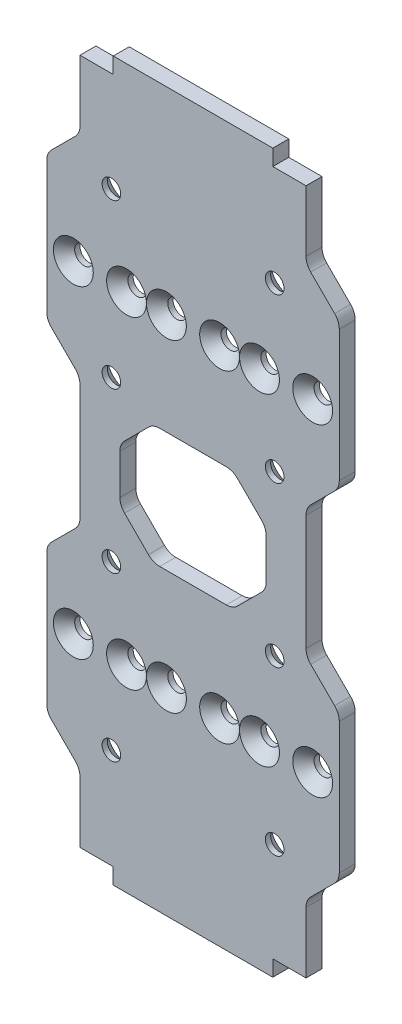
SolidWorks part; units mm, degrees
material "ABS"
ref_plane "Спереди" through (0, 0, 0) normal (0, 0, 1) x (1, 0, 0)
ref_plane "Сверху" through (0, 0, 0) normal (0, 1, 0) x (1, 0, 0)
ref_plane "Справа" through (0, 0, 0) normal (1, 0, 0) x (0, 0, -1)
sketch "Эскиз1" plane through (0, 0, 0) normal (0, 0, 1) x (1, 0, 0)
  line L0 (-27.5, 0) -> (27.5, 0) construction
  line L1 (-27.5, -64.5) -> (27.5, -64.5)
  line L2 (-27.5, -64.5) -> (-27.5, 64.5)
  line L3 (-27.5, 64.5) -> (27.5, 64.5)
  line L4 (27.5, -64.5) -> (27.5, 64.5)
  line L5 (-27.5, -64.5) -> (27.5, 64.5) construction
  line L6 (-27.5, 64.5) -> (27.5, -64.5) construction
  line L7 (-15, 61.5) -> (15, 61.5)
  line L8 (-15, 61.5) -> (-15, 67.5)
  line L9 (-15, 67.5) -> (15, 67.5)
  line L10 (15, 61.5) -> (15, 67.5)
  line L11 (-15, 61.5) -> (15, 67.5) construction
  line L12 (-15, 67.5) -> (15, 61.5) construction
  line L13 (-15, -67.5) -> (15, -61.5) construction
  line L14 (-15, -61.5) -> (15, -67.5) construction
  line L15 (15, -61.5) -> (15, -67.5)
  line L16 (-15, -67.5) -> (15, -67.5)
  line L17 (-15, -61.5) -> (-15, -67.5)
  line L18 (-15, -61.5) -> (15, -61.5)
  point P0 (0, 0)
  point P6 (0, 64.5)
  point P17 (0, -64.5)
  dimension "D1" = 3
  dimension "D2" = 30
  dimension "D3" = 12.5
  dimension "D4" = 129
extrude "Бобышка-Вытянуть1" add sketch "Эскиз1" along normal blind 3 contours L10 L7 L8 L3 L2 L1 L4 | L7 L10 L3 L8 | L3 L10 L9 L8 | L18 L17 L1 L15 | L1 L17 L16 L15 region at (0, 0, 0) region at (0, -63, 0) region at (0, -66, 0) region at (0, 66, 0) region at (0, 63, 0)
sketch "Эскиз2" plane through (0, 0, 3) normal (0, 0, 1) x (1, 0, 0)
  line L0 (0, 67.5) -> (0, -67.5) construction
  line L1 (-15, 67.5) -> (15, 67.5) construction
  line L3 (-27.5, 0) -> (27.5, 0) construction
  line L4 (-27.5, -64.5) -> (-27.5, 64.5) construction
  line L5 (27.5, -64.5) -> (27.5, 64.5) construction
  line L6 (-15.35, -15) -> (15.35, -45.7) construction
  line L7 (-15.35, 45.7) -> (15.35, 45.7) construction
  line L8 (-15.35, 45.7) -> (-15.35, 15) construction
  line L9 (-15.35, 15) -> (15.35, 15) construction
  line L10 (15.35, 45.7) -> (15.35, 15) construction
  line L11 (-15.35, 45.7) -> (15.35, 15) construction
  line L12 (-15.35, 15) -> (15.35, 45.7) construction
  line L13 (-15.35, -45.7) -> (15.35, -15) construction
  line L14 (15.35, -45.7) -> (15.35, -15) construction
  line L15 (-15.35, -15) -> (15.35, -15) construction
  line L16 (-15.35, -45.7) -> (-15.35, -15) construction
  line L17 (-15.35, -45.7) -> (15.35, -45.7) construction
  line L18 (-15, -67.5) -> (15, -67.5) construction
  circle A0 centre (-15.35, 45.7) radius 1.75
  circle A1 centre (15.35, 45.7) radius 1.75
  circle A2 centre (15.35, 15) radius 1.75
  circle A3 centre (-15.35, 15) radius 1.75
  circle A4 centre (-15.35, -15) radius 1.75
  circle A5 centre (15.35, -15) radius 1.75
  circle A6 centre (15.35, -45.7) radius 1.75
  circle A7 centre (-15.35, -45.7) radius 1.75
  point P4 (0, -65.5)
  point P12 (0, 30.35)
  point P29 (0, -30.35)
  dimension "D3" = 3.5
  dimension "D1" = 30.7
  dimension "D2" = 30.7
  dimension "D4" = 15
extrude "Вырез-Вытянуть1" cut sketch "Эскиз2" against normal blind 10
sketch "Эскиз3" plane through (0, 0, 0) normal (0, 0, -1) x (-1, 0, 0)
  line L0 (-15.35, 15) -> (15.35, 45.7) construction
  line L1 (-27.5, 30.35) -> (27.5, 30.35) construction
  line L2 (-27.5, -64.5) -> (-27.5, 64.5) construction
  line L3 (27.5, -64.5) -> (27.5, 64.5) construction
  line L4 (-27.5, 0) -> (27.5, 0) construction
  line L5 (-27.5, -30.35) -> (27.5, -30.35) construction
  line L6 (-15.35, -15) -> (15.35, -45.7) construction
  circle A0 centre (-22.5, 30.35) radius 1.75
  circle A1 centre (-12.5, 30.35) radius 1.75
  circle A2 centre (-5, 30.35) radius 1.75
  circle A3 centre (5, 30.35) radius 1.75
  circle A4 centre (12.5, 30.35) radius 1.75
  circle A5 centre (22.5, 30.35) radius 1.75
  circle A6 centre (22.5, -30.35) radius 1.75
  circle A7 centre (12.5, -30.35) radius 1.75
  circle A8 centre (5, -30.35) radius 1.75
  circle A9 centre (-5, -30.35) radius 1.75
  circle A10 centre (-12.5, -30.35) radius 1.75
  circle A11 centre (-22.5, -30.35) radius 1.75
  point P10 (0, 30.35)
  dimension "D1" = 3.5
  dimension "D2" = 3.5
  dimension "D3" = 10
  dimension "D5" = 5
  dimension "D6" = 7.5
  dimension "D4" = 3
extrude "Вырез-Вытянуть2" cut sketch "Эскиз3" against normal blind 10
chamfer "Фаска1" distance 2 angle 45 8 edges at (-13.6, 45.7, 0) (-13.6, 15, 0) (17.1, 45.7, 0) (17.1, 15, 0) (-13.6, -45.7, 0) (17.1, -45.7, 0) (-13.6, -15, 0) (17.1, -15, 0)
chamfer "Фаска2" distance 2 angle 45 12 edges at (24.25, 30.35, 3) (14.25, 30.35, 3) (6.75, 30.35, 3) (-3.25, 30.35, 3) (-10.75, 30.35, 3) (-20.75, 30.35, 3) (24.25, -30.35, 3) (14.25, -30.35, 3) (6.75, -30.35, 3) (-3.25, -30.35, 3) (-10.75, -30.35, 3) (-20.75, -30.35, 3)
sketch "Эскиз4" plane through (0, 0, 0) normal (0, 0, -1) x (-1, 0, 0)
  line L0 (0, -67.5) -> (0, 67.5) construction
  line L3 (15, -67.5) -> (-15, -67.5) construction
  line L4 (15, 67.5) -> (-15, 67.5) construction
  line L5 (-27.5, 0) -> (27.5, 0) construction
  line L6 (-27.5, -64.5) -> (-27.5, 64.5) construction
  line L7 (27.5, -64.5) -> (27.5, 64.5) construction
  line L8 (7.5, 11.25) -> (-7.5, 11.25)
  line L9 (-7.5, 11.25) -> (-13.75, 5)
  line L10 (-13.75, 5) -> (-13.75, -5)
  line L11 (13.75, 5) -> (13.75, -5)
  line L12 (7.5, 11.25) -> (13.75, 5)
  line L13 (7.5, -11.25) -> (13.75, -5)
  line L14 (-7.5, -11.25) -> (-13.75, -5)
  line L15 (7.5, -11.25) -> (-7.5, -11.25)
  point P20 (0, 11.25)
  point P22 (13.75, 0)
  point P23 (-13.75, 0)
  point P24 (0, -11.25)
  dimension "D1" = 135
  dimension "D2" = 10
  dimension "D3" = 15
  dimension "D4" = 22.5
extrude "Вырез-Вытянуть3" cut sketch "Эскиз4" against normal blind 3
sketch "Эскиз6" plane through (0, 0, 3) normal (0, 0, 1) x (1, 0, 0)
  line L0 (21.25, 64.5) -> (21.25, 51.75)
  line L1 (15, 64.5) -> (27.5, 64.5) construction
  line L2 (21.25, 51.75) -> (27.5, 45.5)
  line L3 (27.5, -64.5) -> (27.5, 64.5) construction
  line L4 (0, 67.5) -> (0, -67.5) construction
  line L5 (-15, 67.5) -> (15, 67.5) construction
  line L6 (-15, -67.5) -> (15, -67.5) construction
  line L7 (-27.5, 0) -> (27.5, 0) construction
  line L8 (-27.5, -64.5) -> (-27.5, 64.5) construction
  line L9 (21.25, 64.5) -> (29.2226, 64.5)
  line L10 (29.2226, 64.5) -> (29.2226, 45.5)
  line L11 (29.2226, 45.5) -> (27.5, 45.5)
  line L12 (-29.2226, 45.5) -> (-27.5, 45.5)
  line L13 (-29.2226, 64.5) -> (-29.2226, 45.5)
  line L14 (-21.25, 64.5) -> (-29.2226, 64.5)
  line L15 (-21.25, 51.75) -> (-27.5, 45.5)
  line L16 (-21.25, 64.5) -> (-21.25, 51.75)
  line L17 (-21.25, -64.5) -> (-21.25, -51.75)
  line L18 (-21.25, -51.75) -> (-27.5, -45.5)
  line L19 (-21.25, -64.5) -> (-29.2226, -64.5)
  line L20 (-29.2226, -64.5) -> (-29.2226, -45.5)
  line L21 (-29.2226, -45.5) -> (-27.5, -45.5)
  line L22 (29.2226, -45.5) -> (27.5, -45.5)
  line L23 (29.2226, -64.5) -> (29.2226, -45.5)
  line L24 (21.25, -64.5) -> (29.2226, -64.5)
  line L25 (21.25, -51.75) -> (27.5, -45.5)
  line L26 (21.25, -64.5) -> (21.25, -51.75)
  line L27 (-27.5, 18.35) -> (-21.25, 12.1)
  line L28 (-21.25, 12.1) -> (-21.25, -12.1)
  line L29 (-22.5, 30.35) -> (22.5, 30.35) construction
  line L30 (-27.5, -18.35) -> (-21.25, -12.1)
  line L31 (27.5, -18.35) -> (21.25, -12.1)
  line L32 (21.25, 12.1) -> (21.25, -12.1)
  line L33 (27.5, 18.35) -> (21.25, 12.1)
  line L34 (-27.5, 18.35) -> (-29.8345, 18.35)
  line L35 (-29.8345, 18.35) -> (-29.8345, -18.35)
  line L36 (-29.8345, -18.35) -> (-27.5, -18.35)
  line L37 (27.5, 18.35) -> (30.3886, 18.35)
  line L38 (30.3886, 18.35) -> (30.3886, -18.35)
  line L39 (30.3886, -18.35) -> (27.5, -18.35)
  point P43 (-21.25, 0)
  point P47 (21.25, 0)
  dimension "D1" = 135
  dimension "D2" = 19
  dimension "D3" = 135
  dimension "D4" = 12
extrude "Вырез-Вытянуть4" cut sketch "Эскиз6" against normal blind 10
fillet "Скругление1" radius 3 16 edges at (27.5, 18.35, 1.5) (27.5, 45.5, 1.5) (21.25, 51.75, 1.5) (-21.25, 51.75, 1.5) (-27.5, 45.5, 1.5) (-27.5, 18.35, 1.5) (-21.25, 12.1, 1.5) (-21.25, -12.1, 1.5) (-27.5, -18.35, 1.5) (-27.5, -45.5, 1.5) (-21.25, -51.75, 1.5) (21.25, -51.75, 1.5) (27.5, -45.5, 1.5) (27.5, -18.35, 1.5) (21.25, -12.1, 1.5) (21.25, 12.1, 1.5)
fillet "Скругление2" radius 3 8 edges at (7.5, -11.25, 1.5) (13.75, -5, 1.5) (-7.5, -11.25, 1.5) (-13.75, -5, 1.5) (-13.75, 5, 1.5) (-7.5, 11.25, 1.5) (7.5, 11.25, 1.5) (13.75, 5, 1.5)
